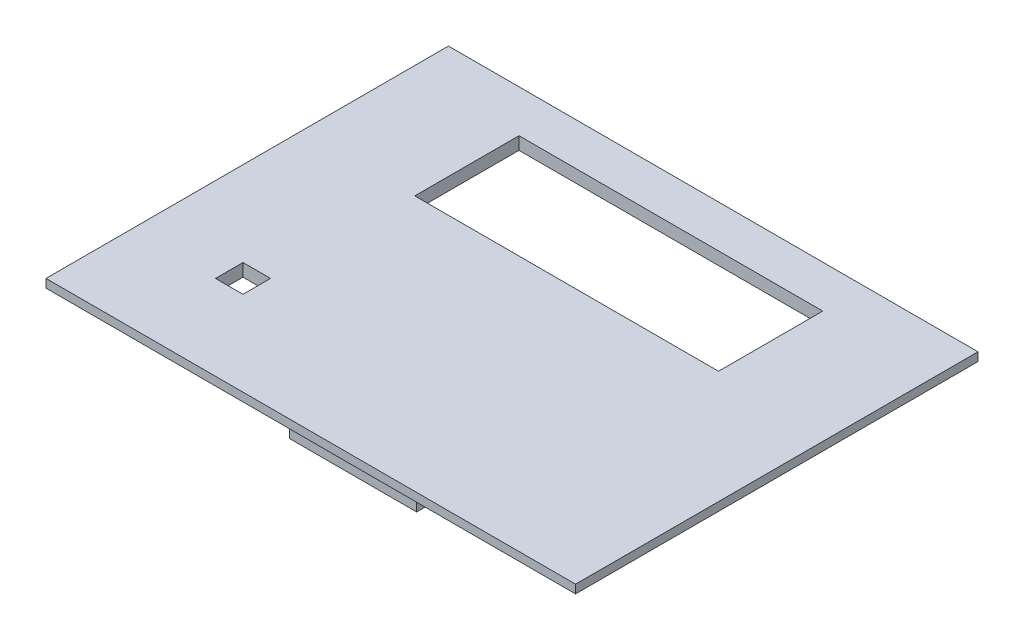
SolidWorks part; units mm, degrees
ref_plane "Plano frontal" through (0, 0, 0) normal (0, 0, 1) x (1, 0, 0)
ref_plane "Plano superior" through (0, 0, 0) normal (0, 1, 0) x (1, 0, 0)
ref_plane "Plano direito" through (0, 0, 0) normal (1, 0, 0) x (0, 0, -1)
sketch "Esboço1" plane through (0, 0, 0) normal (0, 1, 0) x (1, 0, 0)
  line L1 (-57.5, -42.5) -> (57.5, -42.5)
  line L2 (-57.5, -42.5) -> (-57.5, 42.5)
  line L3 (-57.5, 42.5) -> (57.5, 42.5)
  line L4 (57.5, -42.5) -> (57.5, 42.5)
  line L5 (-57.5, -42.5) -> (57.5, 42.5) construction
  line L6 (-57.5, 42.5) -> (57.5, -42.5) construction
  point P0 (0, 0)
  dimension "D1" = 115
  dimension "D2" = 85
extrude "Ressalto-extrusão1" add sketch "Esboço1" along normal blind 1
sketch "Esboço2" plane through (0, 1, 0) normal (0, 1, 0) x (1, 0, 0)
  line L1 (-62.5, -47.5) -> (62.5, -47.5)
  line L2 (-62.5, -47.5) -> (-62.5, 47.5)
  line L3 (-62.5, 47.5) -> (62.5, 47.5)
  line L4 (62.5, -47.5) -> (62.5, 47.5)
  line L5 (-62.5, -47.5) -> (62.5, 47.5) construction
  line L6 (-62.5, 47.5) -> (62.5, -47.5) construction
  point P0 (0, 0)
  dimension "D1" = 125
  dimension "D2" = 95
extrude "Ressalto-extrusão2" add sketch "Esboço2" along normal blind 2
sketch "Esboço3" plane through (0, 3, 0) normal (0, 1, 0) x (1, 0, 0)
  line L0 (0, 0) -> (0, 47.5) construction
  line L1 (-35.85, 37.5) -> (35.85, 37.5)
  line L2 (-35.85, 37.5) -> (-35.85, 12.9)
  line L3 (-35.85, 12.9) -> (35.85, 12.9)
  line L4 (35.85, 37.5) -> (35.85, 12.9)
  line L5 (-35.85, 37.5) -> (35.85, 12.9) construction
  line L6 (-35.85, 12.9) -> (35.85, 37.5) construction
  line L7 (62.5, 47.5) -> (-62.5, 47.5) construction
  line L8 (-62.5, 47.5) -> (-62.5, -47.5) construction
  line L10 (-42.5, -27.5) -> (-36, -27.5)
  line L11 (-42.5, -27.5) -> (-42.5, -21)
  line L12 (-42.5, -21) -> (-36, -21)
  line L13 (-36, -27.5) -> (-36, -21)
  line L14 (-42.5, -27.5) -> (-36, -21) construction
  line L15 (-42.5, -21) -> (-36, -27.5) construction
  line L16 (-62.5, -47.5) -> (62.5, -47.5) construction
  point P0 (0, 25.2)
  point P11 (-39.25, -24.25)
  dimension "D1" = 71.7
  dimension "D2" = 24.6
  dimension "D3" = 10
  dimension "D4" = 6.5
  dimension "D5" = 6.5
  dimension "D6" = 20
  dimension "D7" = 20
extrude "Corte-extrusão1" cut sketch "Esboço3" against normal through all
sketch "Esboço5" plane through (0, 0, 0) normal (0, -1, 0) x (1, 0, 0)
  line L0 (-15, 37.5) -> (15, 37.5)
  line L1 (15, 37.5) -> (15, 35.5)
  line L2 (15, 35.5) -> (-15, 35.5)
  line L3 (-15, 35.5) -> (-15, 37.5)
  line L4 (-15, -5.5) -> (-15, -7.5)
  line L5 (-15, -7.5) -> (15, -7.5)
  line L6 (15, -7.5) -> (15, -5.5)
  line L7 (15, -5.5) -> (-15, -5.5)
  line L8 (0, 0) -> (0, 42.5) construction
  line L9 (-57.5, 42.5) -> (57.5, 42.5) construction
  point P14 (0, 37.5)
  point P15 (0, -5.5)
  dimension "D1" = 2
  dimension "D2" = 30
  dimension "D3" = 41
  dimension "D4" = 5
extrude "Ressalto-extrusão3" add sketch "Esboço5" along normal blind 9
sketch "Esboço6" plane through (0, -9, 0) normal (0, -1, 0) x (-1, 0, 0)
  line L0 (-15, -37.5) -> (-15, -32.5)
  line L1 (-15, -32.5) -> (15, -32.5)
  line L2 (15, -32.5) -> (15, -37.5)
  line L3 (15, -37.5) -> (-15, -37.5)
  line L4 (-15, 7.5) -> (-15, 2.5)
  line L5 (-15, 2.5) -> (15, 2.5)
  line L6 (15, 2.5) -> (15, 7.5)
  line L7 (15, 7.5) -> (-15, 7.5)
  dimension "D1" = 5
  dimension "D2" = 5
extrude "Ressalto-extrusão4" add sketch "Esboço6" along normal blind 2
